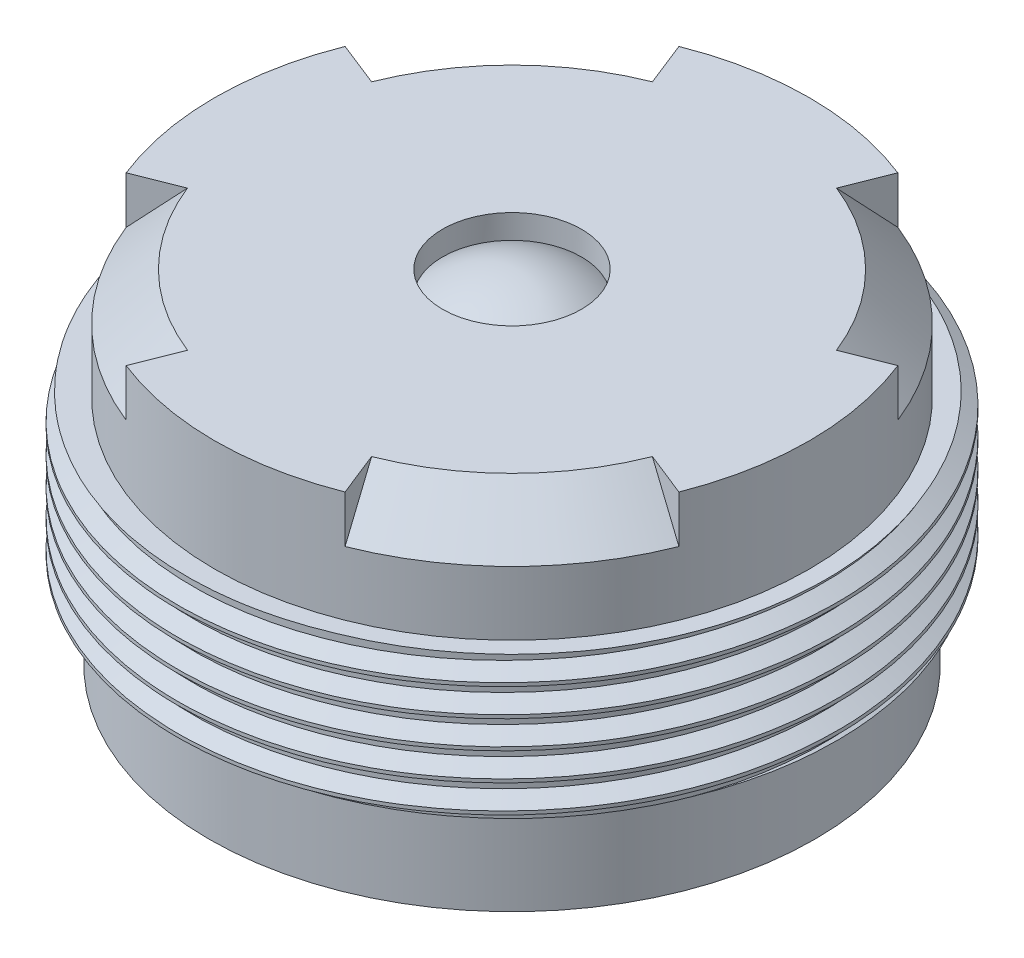
SolidWorks part; units mm, degrees
ref_plane "Front Plane" through (0, 0, 0) normal (0, 0, 1) x (1, 0, 0)
ref_plane "Top Plane" through (0, 0, 0) normal (0, 1, 0) x (1, 0, 0)
ref_plane "Right Plane" through (0, 0, 0) normal (1, 0, 0) x (0, 0, -1)
sketch "Sketch1" plane through (0, 0, 0) normal (0, 1, 0) x (1, 0, 0)
  circle A0 centre (0, 0) radius 2.725
  dimension "D1" = 5.45
extrude "Boss-Extrude1" add sketch "Sketch1" along normal blind 3.08
sketch "Sketch2" plane through (0, 0, 0) normal (0, -1, 0) x (1, 0, 0)
  circle A0 centre (0, 0) radius 2.11
  dimension "D1" = 4.22
extrude "Cut-Extrude1" cut sketch "Sketch2" against normal blind 2.08
sketch "Sketch3" plane through (0, 3.08, 0) normal (0, 1, 0) x (1, 0, 0)
  circle A0 centre (0, 0) radius 0.625
  dimension "D1" = 1.25
extrude "Cut-Extrude2" cut sketch "Sketch3" against normal up to next
sketch "Sketch4" plane through (0, 3.08, 0) normal (0, 1, 0) x (1, 0, 0)
  circle A0 centre (0, 0) radius 2.675
  circle A1 centre (0, 0) radius 2.725
  dimension "D1" = 5.35
extrude "Cut-Extrude3" cut sketch "Sketch4" against normal blind 1
sketch "Sketch5" plane through (0, 3.08, 0) normal (0, 1, 0) x (1, 0, 0)
  line L0 (0, 0) -> (0, 2.675) construction
  line L1 (0, 0) -> (0.985, 2.487)
  line L2 (0, 0) -> (-0.985, 2.487)
  line L3 (-0.985, 2.487) -> (0.985, 2.487) construction
  line L4 (0, 0) -> (2.487, -0.985)
  line L5 (0, 0) -> (2.487, 0.985)
  line L6 (0, 0) -> (-0.985, -2.487)
  line L7 (0, 0) -> (0.985, -2.487)
  line L8 (0, 0) -> (-2.487, 0.985)
  line L9 (0, 0) -> (-2.487, -0.985)
  circle A0 centre (0, 0) radius 2.675
  circle A1 centre (0, 0) radius 2.25
  circle A2 centre (0, 0) radius 2.675 construction
  point P3 (0, 2.487)
  point P19 (0, 0)
  dimension "D2" = 4.5
  dimension "D1" = 1.97
  dimension "D3" = 4
sketch "Sketch6" plane through (0, 3.08, 0) normal (0, 1, 0) x (1, 0, 0)
  line L0 (0, 0) -> (2.487, 0.985) construction
  line L1 (0, 0) -> (2.487, -0.985) construction
  line L2 (0, 0) -> (0.985, -2.487) construction
  line L3 (0, 0) -> (-0.985, -2.487) construction
  line L4 (0, 0) -> (-2.487, -0.985) construction
  line L5 (0, 0) -> (-2.487, 0.985) construction
  line L6 (0, 0) -> (-0.985, 2.487) construction
  line L7 (0, 0) -> (0.985, 2.487) construction
  line L8 (2.0919, 0.8285) -> (2.487, 0.985)
  line L9 (2.0919, -0.8285) -> (2.487, -0.985)
  line L10 (0.8285, -2.0919) -> (0.985, -2.487)
  line L11 (-0.8285, -2.0919) -> (-0.985, -2.487)
  line L12 (-2.0919, -0.8285) -> (-2.487, -0.985)
  line L13 (-2.0919, 0.8285) -> (-2.487, 0.985)
  line L14 (-0.8285, 2.0919) -> (-0.985, 2.487)
  line L15 (0.8285, 2.0919) -> (0.985, 2.487)
  circle A0 centre (0, 0) radius 2.675 construction
  circle A1 centre (0, 0) radius 2.25 construction
  arc A2 (-0.985, 2.487) -> (-2.487, 0.985) centre (0, 0) ccw
  arc A3 (-0.8285, 2.0919) -> (-2.0919, 0.8285) centre (0, 0) ccw
  arc A4 (2.0919, 0.8285) -> (0.8285, 2.0919) centre (0, 0) ccw
  arc A5 (2.487, 0.985) -> (0.985, 2.487) centre (0, 0) ccw
  arc A6 (-2.0919, -0.8285) -> (-0.8285, -2.0919) centre (0, 0) ccw
  arc A7 (-2.487, -0.985) -> (-0.985, -2.487) centre (0, 0) ccw
  arc A8 (0.8285, -2.0919) -> (2.0919, -0.8285) centre (0, 0) ccw
  arc A9 (0.985, -2.487) -> (2.487, -0.985) centre (0, 0) ccw
extrude "Cut-Extrude4" cut sketch "Sketch6" against normal blind 1
sketch "Sketch7" plane through (0, 2.08, 0) normal (0, 1, 0) x (1, 0, 0)
  line L0 (2.487, -0.985) -> (2.0919, -0.8285) construction
  line L1 (0.8285, -2.0919) -> (0.985, -2.487) construction
  line L2 (2.487, -0.985) -> (2.0919, -0.8285)
  line L3 (0.8285, -2.0919) -> (0.985, -2.487)
  line L4 (2.0919, 0.8285) -> (2.487, 0.985) construction
  line L5 (0.985, 2.487) -> (0.8285, 2.0919) construction
  line L6 (2.0919, 0.8285) -> (2.487, 0.985)
  line L7 (0.985, 2.487) -> (0.8285, 2.0919)
  line L8 (-0.8285, 2.0919) -> (-0.985, 2.487) construction
  line L9 (-2.487, 0.985) -> (-2.0919, 0.8285) construction
  line L10 (-0.8285, 2.0919) -> (-0.985, 2.487)
  line L11 (-2.487, 0.985) -> (-2.0919, 0.8285)
  line L12 (-2.0919, -0.8285) -> (-2.487, -0.985) construction
  line L13 (-0.985, -2.487) -> (-0.8285, -2.0919) construction
  line L14 (-2.0919, -0.8285) -> (-2.487, -0.985)
  line L15 (-0.985, -2.487) -> (-0.8285, -2.0919)
  circle A0 centre (0, 0) radius 2.25 construction
  circle A1 centre (0, 0) radius 2.675 construction
  arc A2 (0.8285, -2.0919) -> (2.0919, -0.8285) centre (0, 0) ccw
  arc A3 (0.985, -2.487) -> (2.487, -0.985) centre (0, 0) ccw
  arc A4 (-0.8285, 2.0919) -> (-2.0919, 0.8285) centre (0, 0) ccw
  arc A5 (-0.985, 2.487) -> (-2.487, 0.985) centre (0, 0) ccw
  arc A6 (-2.487, -0.985) -> (-0.985, -2.487) centre (0, 0) ccw
  arc A7 (-2.0919, -0.8285) -> (-0.8285, -2.0919) centre (0, 0) ccw
  arc A8 (2.0919, 0.8285) -> (0.8285, 2.0919) centre (0, 0) ccw
  arc A9 (2.487, 0.985) -> (0.985, 2.487) centre (0, 0) ccw
extrude "Boss-Extrude2" add sketch "Sketch7" along normal blind 0.5
chamfer "Chamfer1" distance 0.5 4 edges at (-1.591, 2.58, 1.591) (-1.591, 2.58, -1.591) (1.591, 2.58, -1.591) (1.591, 2.58, 1.591)
ref_plane "Plane1" through (0, 0.8, 0) normal (0, 1, 0) x (1, 0, 0)
sketch "Sketch8" plane through (0, 0.8, 0) normal (0, 1, 0) x (1, 0, 0)
  circle A0 centre (0, 0) radius 2.965
  circle A1 centre (0, 0) radius 2.11 construction
  circle A2 centre (0, 0) radius 2.11
  dimension "D1" = 5.93
extrude "Boss-Extrude3" add sketch "Sketch8" along normal up to surface (1.28 mm away) up to face at (0, 2.08, 2.725)
thread "Thread1" pitch 0.25 method cut profile "Thread Profile1" start angle 0, offset 0.5, length 2, pitch 0.25, diameter 5.93
ref_plane "Plane2" through (-2.965, 2.58, 0) normal (0, 0, 1) x (-1, 0, 0)
sketch "Thread Profile1" plane through (-2.965, 2.58, 0) normal (0, 0, 1) x (-1, 0, 0)
  line L0 (0, 0) -> (0, 0.25) construction
  line L11 (0, 0) -> (0, 0.2187)
  line L12 (0, 0.2187) -> (-0.1353, 0.1406)
  line L13 (-0.1353, 0.1406) -> (-0.1353, 0.0781)
  line L15 (-0.1353, 0.0781) -> (0, 0)
  line L17 (-0.1353, 0.1094) -> (0, 0.1094) construction
  point P2 (0, 0)
  dimension "Pitch" = 0.25
  dimension "Profile_Angle" = 60
  dimension "Profile_Land" = 0.0625
  dimension "Profile_Height" = 0.1353
sketch "Sketch11" plane through (0, 0, 0) normal (0, 0, 1) x (1, 0, 0)
  line L0 (0, 0) -> (0, 3.08) construction
  line L1 (-0.8285, 3.08) -> (-0.985, 3.08) construction
  point P3 (0, 0)
sketch "Sketch12" plane through (0, 0, 0) normal (1, 0, 0) x (0, 0, -1)
  line L0 (0.625, 3.08) -> (-0.625, 3.08) construction
  line L1 (0.625, 3.08) -> (-0.625, 3.08) construction
  line L2 (-0.625, 2.8635) -> (0.625, 2.8635) construction
  line L3 (0, 0) -> (0, 3.08) construction
  line L4 (-0.625, 2.651) -> (0.625, 2.651) construction
  line L5 (-0.625, 2.8635) -> (-0.625, 2.651) construction
  line L6 (0.625, 2.8635) -> (0.625, 2.651)
  line L7 (-0.625, 2.7572) -> (0.625, 2.7572) construction
  line L8 (0, 3.08) -> (0, 2.8635) construction
  line L9 (0, 2.651) -> (0, 2.4344) construction
  line L10 (0, 3.08) -> (0, 2.4344)
  spline S0 degree 2 poles (0.625, 2.8635) (0.3125, 3.08) (0, 3.08) knots 0 0 0 0.5 0.5 0.5
  spline S1 degree 2 poles (0, 2.4344) (0.3125, 2.4344) (0.625, 2.651) knots 0.5 0.5 0.5 1 1 1
  point P4 (0, 2.8635)
revolve "Revolve4" add sketch "Sketch12" angle 360 about L0
